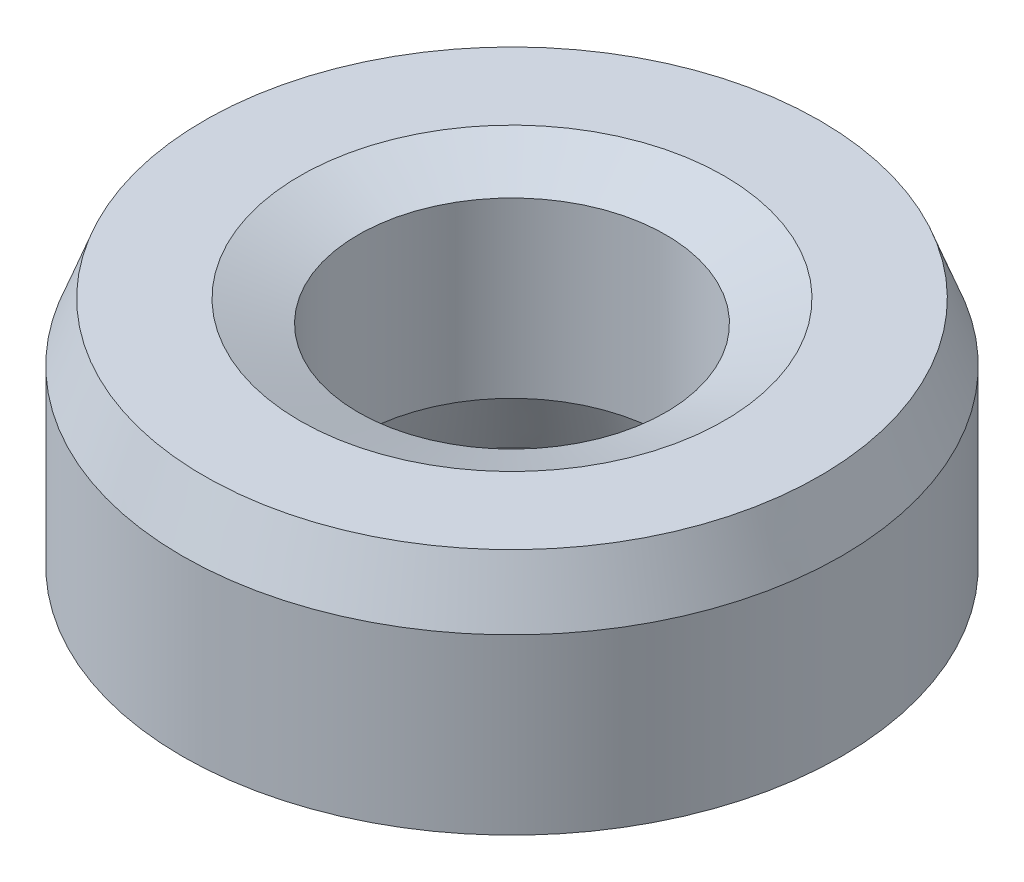
SolidWorks part; units mm, degrees
ref_plane "Front Plane" through (0, 0, 0) normal (0, 0, 1) x (1, 0, 0)
ref_plane "Top Plane" through (0, 0, 0) normal (0, 1, 0) x (1, 0, 0)
ref_plane "Right Plane" through (0, 0, 0) normal (1, 0, 0) x (0, 0, -1)
sketch "Sketch1" plane through (0, 0, 0) normal (0, 1, 0) x (1, 0, 0)
  circle A0 centre (0, 0) radius 10
  dimension "SLEEVE_OD" = 20
extrude "Boss-Extrude1" add sketch "Sketch1" along normal blind 7.6942
sketch "Sketch2" plane through (0, 0, 0) normal (0, 1, 0) x (1, 0, 0)
  circle A0 centre (0, 0) radius 4.6648
  dimension "BORE_D" = 9.3297
extrude "Cut-Extrude1" cut sketch "Sketch2" along normal through all
chamfer "Chamfer1" distance 1.7697 angle 20.534 4 edges at (0, 7.6942, 4.6648) (0, 0, 4.6648) (0, 0, 10) (0, 7.6942, 10) first distance on face at (0, 7.6942, 4.6648) first distance on face at (0, 0, 4.6648) first distance on face at (0, 7.6942, 10)
